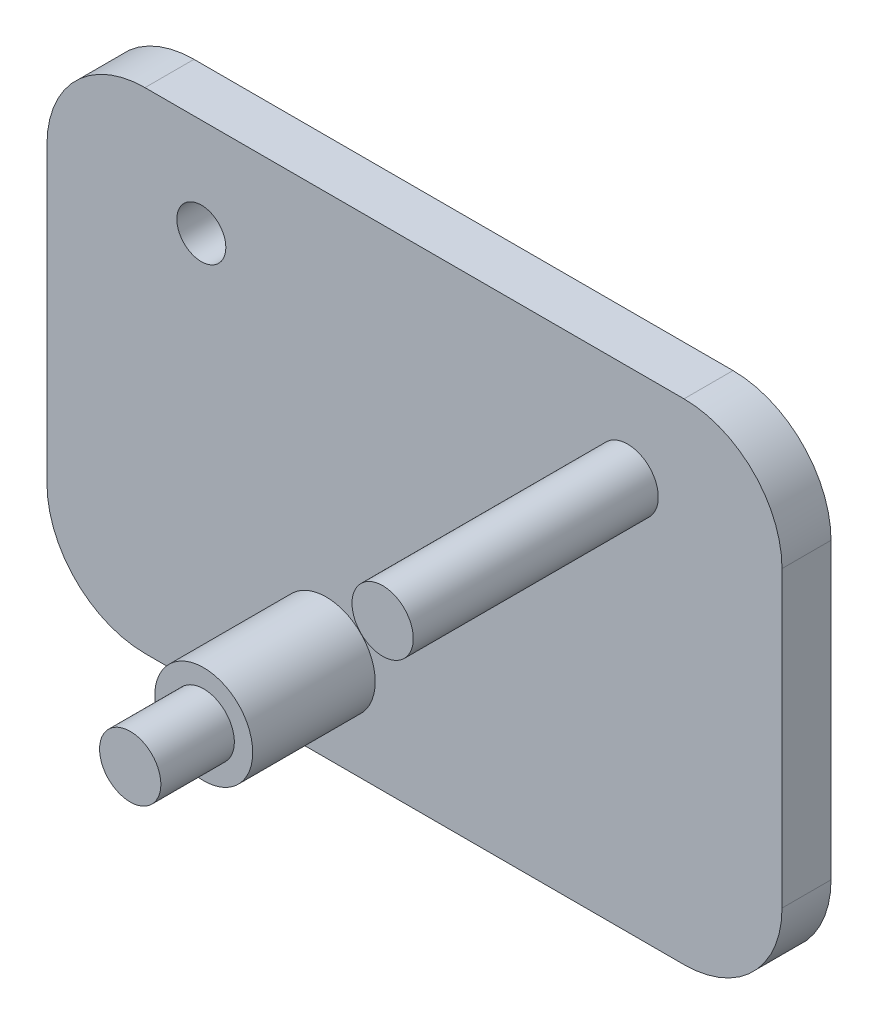
SolidWorks part; units mm, degrees
ref_plane "Front Plane" through (0, 0, 0) normal (0, 0, 1) x (1, 0, 0)
ref_plane "Top Plane" through (0, 0, 0) normal (0, 1, 0) x (1, 0, 0)
ref_plane "Right Plane" through (0, 0, 0) normal (1, 0, 0) x (0, 0, -1)
sketch "Sketch1" plane through (0, 0, 0) normal (0, 0, 1) x (1, 0, 0)
  line L0 (-38.1, 0) -> (-38.1, -25.4)
  line L3 (0, 0) -> (-38.1, 0)
  line L6 (-38.1, -25.4) -> (0, -25.4)
  line L7 (0, -25.4) -> (0, 0)
  point P0 (-19.05, 0)
  point P5 (0, 0)
  point P7 (0, 0)
  point P8 (-31.0339, -25.4)
  dimension "D1" = 25.4
  dimension "D2" = 38.1
extrude "Boss-Extrude1" add sketch "Sketch1" along normal blind 2.54 contours L3 L0 L6 L7
sketch "Sketch2" plane through (0, 0, 2.54) normal (0, 0, 1) x (1, 0, 0)
  line L0 (0, -25.4) -> (0, 0) construction
  line L1 (0, 0) -> (-38.1, 0) construction
  line L2 (0, -5.08) -> (-38.1, -5.08) construction
  line L3 (-8.001, -5.08) -> (-30.099, -5.08) construction
  line L7 (-38.1, 0) -> (-38.1, -25.4) construction
  line L8 (-8.001, -5.08) -> (-23.6266, -20.7056) construction
  circle A1 centre (-8.001, -5.08) radius 1.5875
  circle A2 centre (-23.6266, -20.7056) radius 1.5875
  circle A3 centre (-30.099, -5.08) radius 1.27
  point P4 (-19.05, -5.08)
  point P5 (-19.05, -5.08)
  point P8 (-19.05, 0)
  point P14 (-19.05, -5.08)
  dimension "D1" = 3.175
  dimension "D2" = 2.54
  dimension "D3" = 5.08
  dimension "D4" = 45
  dimension "D6" = 3.175
  dimension "D5" = 22.098
  dimension "D7" = 22.098
extrude "Boss-Extrude2" add sketch "Sketch2" along normal blind 12.7
sketch "Sketch5" plane through (0, 0, 15.24) normal (0, 0, 1) x (1, 0, 0)
  circle A0 centre (-30.099, -5.08) radius 1.27
  dimension "D1" = 2.54
extrude "Cut-Extrude1" cut sketch "Sketch5" against normal through all
sketch "Sketch6" plane through (0, 0, 2.54) normal (0, 0, 1) x (1, 0, 0)
  circle A0 centre (-23.6266, -20.7056) radius 2.54
  dimension "D1" = 5.08
extrude "Boss-Extrude3" add sketch "Sketch6" along normal blind 6.35
sketch "Sketch7" plane through (0, 0, 15.24) normal (0, 0, 1) x (1, 0, 0)
  circle A1 centre (-23.6266, -20.7056) radius 1.5875
  dimension "D1" = 3.175
extrude "Cut-Extrude2" cut sketch "Sketch7" against normal blind 2.54
fillet "Fillet1" radius 5.08 4 edges at (0, 0, 1.27) (0, -25.4, 1.27) (-38.1, 0, 1.27) (-38.1, -25.4, 1.27)
